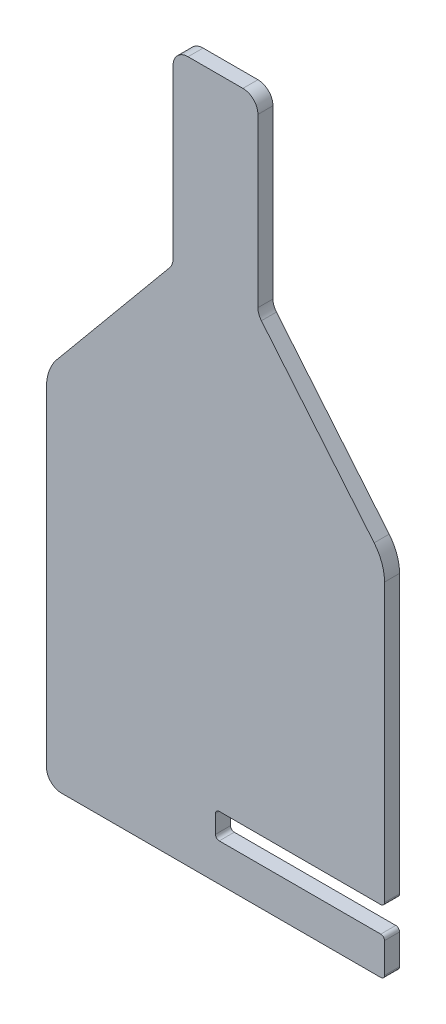
SolidWorks part; units mm, degrees
ref_plane "Alzado" through (0, 0, 0) normal (0, 0, 1) x (1, 0, 0)
ref_plane "Planta" through (0, 0, 0) normal (0, 1, 0) x (1, 0, 0)
ref_plane "Vista lateral" through (0, 0, 0) normal (1, 0, 0) x (0, 0, -1)
sketch "Croquis1" plane through (0, 0, 0) normal (0, 0, 1) x (1, 0, 0)
  line L0 (-5.65, 20) -> (-22.5, -0.3233)
  line L1 (-5.65, 45) -> (5.65, 45)
  line L2 (-22.5, -0.3233) -> (-22.5, -48.3233)
  line L3 (-22.5, -48.3233) -> (22.5, -48.3233)
  line L4 (22.5, -0.3233) -> (22.5, -48.3233)
  line L5 (-5.65, 45) -> (5.65, 45)
  line L6 (-5.65, 45) -> (-5.65, 20)
  line L8 (5.65, 45) -> (5.65, 19.9991)
  line L9 (5.65, 19.9991) -> (22.5, -0.3233)
  line L10 (0, 75.1867) -> (0, -77.6145) construction
  dimension "D1" = 45
  dimension "D2" = 25
  dimension "D3" = 5.65
  dimension "D4" = 22.5
  dimension "D5" = 45
  dimension "D6" = 5.65
  dimension "D7" = 26.3993
  dimension "D8" = 26.4
  dimension "D9" = 48
  dimension "D10" = 48
extrude "Saliente-Extruir1" add sketch "Croquis1" along normal blind 2 contours L6 L0 L2 L3 L4 L9 L8 L1
sketch "Croquis3" plane through (0, 0, 2) normal (0, 0, 1) x (1, 0, 0)
  line L0 (22.5, -0.3233) -> (22.5, -48.3233) construction
  line L1 (22.5, -39.9233) -> (0, -39.9233)
  line L2 (22.5, -39.9233) -> (22.5, -43.3233)
  line L3 (22.5, -43.3233) -> (0, -43.3233)
  line L4 (0, -39.9233) -> (0, -43.3233)
  line L5 (-22.5, -48.3233) -> (22.5, -48.3233) construction
  dimension "D1" = 3.4
  dimension "D2" = 5
  dimension "D3" = 22.5
extrude "Cortar-Extruir2" cut sketch "Croquis3" against normal up to surface (2 mm away) up to face at (0, 4.0882, 0)
fillet "Redondeo1" radius 2 5 edges at (-22.5, -48.3233, 1) (-5.65, 20, 1) (-5.65, 45, 1) (5.65, 19.9991, 1) (5.65, 45, 1)
fillet "Redondeo2" radius 6 2 edges at (-22.5, -0.3233, 1) (22.5, -0.3233, 1)
fillet "Redondeo3" radius 0.5 5 edges at (0, -39.9233, 1) (0, -43.3233, 1) (22.5, -48.3233, 1) (22.5, -43.3233, 1) (22.5, -39.9233, 1)
